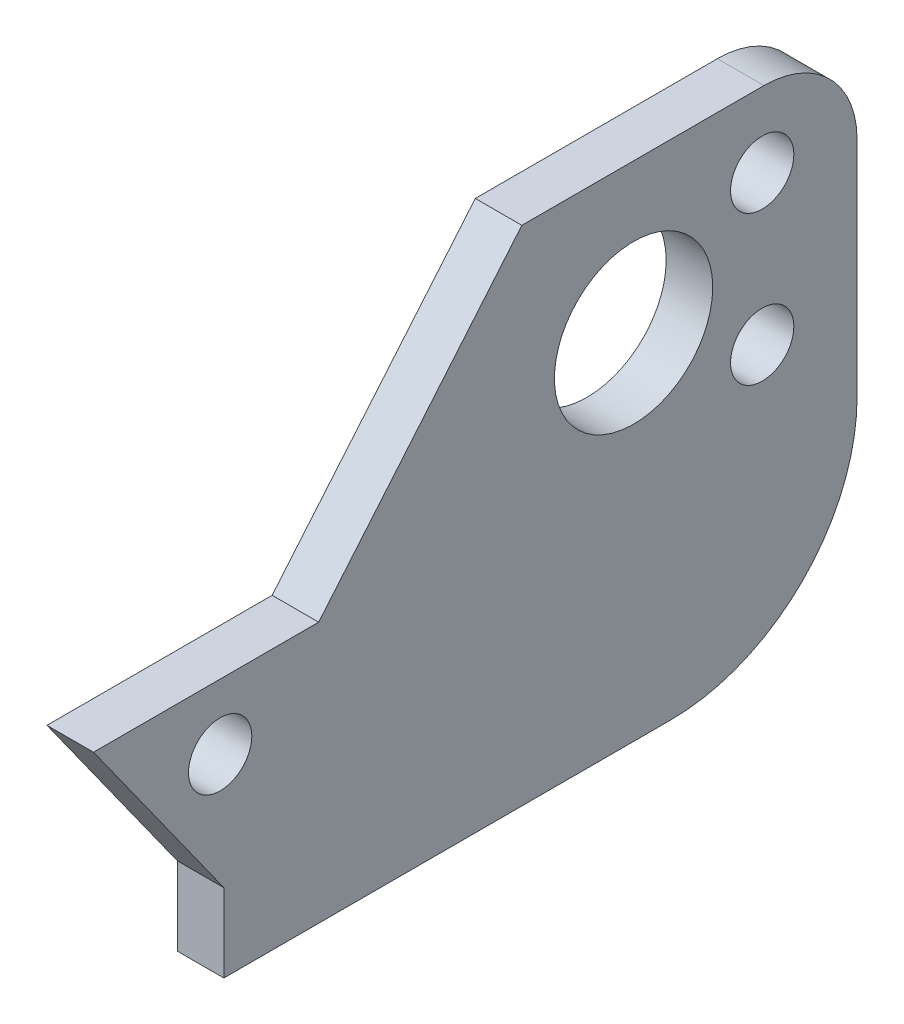
SolidWorks part; units mm, degrees
material "Plain Carbon Steel"
ref_plane "Front Plane" through (0, 0, 0) normal (0, 0, 1) x (1, 0, 0)
ref_plane "Top Plane" through (0, 0, 0) normal (0, 1, 0) x (1, 0, 0)
ref_plane "Right Plane" through (0, 0, 0) normal (1, 0, 0) x (0, 0, -1)
sketch "Sketch1" plane through (0, 0, 0) normal (1, 0, 0) x (0, 0, -1)
  line L0 (-45.1764, 3.0469) -> (-38.7478, -5.9531)
  line L1 (-36.7135, -7) -> (0, -7)
  line L3 (-43.142, 7) -> (0, 7)
  line L4 (0, -7) -> (0, 7)
  line L6 (-18, 20) -> (0, 20)
  line L7 (0, 20) -> (0, 7)
  line L8 (-18, 20) -> (-28.9083, 7)
  arc A2 (-38.7478, -5.9531) -> (-36.7135, -7) centre (-36.7135, -4.5) ccw
  arc A3 (-45.1764, 3.0469) -> (-43.142, 7) centre (-43.142, 4.5) cw
  circle A5 centre (-37.7061, -2.25) radius 1.5
  point P0 (0, 0)
  point P2 (0, 0)
  point P11 (0, 7)
  point P14 (-38, -7)
  point P17 (-48, 7)
  dimension "D4" = 2.5
  dimension "D5" = 3
  dimension "D9" = 4.75
  dimension "D1" = 14
  dimension "D2" = 48
  dimension "D3" = 10
  dimension "D6" = 27
  dimension "D7" = 18
  dimension "D8" = 50
  dimension "D10" = 3
extrude "Boss-Extrude1" add sketch "Sketch1" along normal mid plane 18 contours L7 L6 L3 | A3 L0 A2 L1 L4 L3 region at (0, 0.2529, 21.1769) region at (0, 12.9962, 11.9385)
sketch "Sketch2" plane through (0, 7, 0) normal (0, 1, 0) x (1, 0, 0)
  line L0 (9, -43.142) -> (-9, -43.142) construction
  line L1 (3, -47.142) -> (-3, -47.142)
  line L2 (3, -47.142) -> (3, -43.142)
  line L3 (3, -43.142) -> (-3, -43.142)
  line L4 (-3, -47.142) -> (-3, -43.142)
  line L5 (3, -47.142) -> (-3, -43.142) construction
  line L6 (3, -43.142) -> (-3, -47.142) construction
  point P0 (0, -45.142)
  dimension "D1" = 4
  dimension "D2" = 6
extrude "Boss-Extrude2" add sketch "Sketch2" against normal blind 6
sketch "Sketch3" plane through (3, 0, 0) normal (1, 0, 0) x (0, 0, -1)
  line L0 (-47.142, 1) -> (-47.142, 7) construction
  line L1 (-47.142, 1) -> (-43.7143, 1) construction
  circle A0 centre (-44.142, 4) radius 1.5
  dimension "D1" = 3
  dimension "D2" = 3
  dimension "D3" = 3
extrude "Cut-Extrude1" cut sketch "Sketch3" against normal up to next
fillet "Fillet1" radius 3 2 edges at (0, 1, 47.142) (0, 7, 47.142)
ref_plane "Plane1" through (0, 0, 0) normal (1, 0, 0) x (0, 0, -1)
sketch "Sketch5" plane through (0, 0, 0) normal (1, 0, 0) x (0, 0, -1)
  line L0 (0, 20) -> (0, -7) construction
  line L1 (-18, 20) -> (0, 20) construction
  line L5 (-30.5, -8) -> (6.5, -8)
  line L6 (-30.5, -8) -> (-30.5, 32)
  line L7 (-30.5, 32) -> (6.5, 32)
  line L8 (6.5, -8) -> (6.5, 32)
  line L9 (-30.5, -8) -> (6.5, 32) construction
  line L10 (-30.5, 32) -> (6.5, -8) construction
  circle A0 centre (-12, 12) radius 4.25
  dimension "D1" = 8.5
  dimension "D2" = 12
  dimension "D3" = 37
  dimension "D4" = 8
  dimension "D5" = 40
extrude "Cut-Extrude4" cut sketch "Sketch5" along normal mid plane 13 contours L5 L8 L7 L6 | A0 region at (0, 12, 29.9551)
extrude "Cut-Extrude5" cut sketch "Sketch5<3>" against normal mid plane 25 contours A0
sketch "Sketch5<3>" plane through (0, 0, 0) normal (1, 0, 0) x (0, 0, -1) same geometry as "Sketch5"
fillet "Fillet2" radius 5 1 edges at (-7.75, 20, 0)
sketch "Sketch6" plane through (9, 0, 0) normal (1, 0, 0) x (0, 0, -1)
  line L0 (-48, 7) -> (-38, -7)
  line L8 (-45.1764, 3.0469) -> (-38.7478, -5.9531) construction
  line L9 (-41, 7) -> (-34, -2.8)
  line L11 (-48, 7) -> (-41, 7)
  line L17 (-43.142, 7) -> (-28.9083, 7) construction
  line L18 (-36.7135, -7) -> (0, -7) construction
  line L19 (-34, -2.8) -> (-34, -7)
  line L21 (-38, -7) -> (-34, -7)
  point P0 (-28.9083, 7)
  dimension "D1" = 7
  dimension "D2" = 4
extrude "Cut-Extrude8" cut sketch "Sketch6" against normal up to surface (6 mm away) up to face at (3, 3.9168, 44.9927)
sketch "Sketch8" plane through (-9, 0, 0) normal (-1, 0, 0) x (0, 0, 1)
  line L2 (38, -7) -> (48, 7)
  line L4 (48, 7) -> (41, 7)
  line L5 (43.142, 7) -> (28.9083, 7) construction
  line L6 (41, 7) -> (34, -2.8)
  line L7 (34, -2.8) -> (34, -7)
  line L8 (36.7135, -7) -> (0, -7) construction
  line L9 (34, -7) -> (38, -7)
  dimension "D1" = 7
  dimension "D2" = 4
extrude "Cut-Extrude9" cut sketch "Sketch8" against normal up to surface (6 mm away) up to face at (-3, 3.9168, 44.9927)
sketch "Sketch9" plane through (9, 0, 0) normal (1, 0, 0) x (0, 0, -1)
  line L0 (-5.0949, 16) -> (-5.0949, 8) construction
  arc A1 (-5.0949, 8) -> (-5.0949, 16) centre (-12, 12) ccw
  circle A4 centre (-5.0949, 8) radius 1.7
  circle A5 centre (-5.0949, 16) radius 1.7
  circle A9 centre (-12, 12) radius 4.25 construction
  dimension "D1" = 7.98
  dimension "D4" = 3.4
  dimension "D2" = 8
extrude "Cut-Extrude10" cut sketch "Sketch9" against normal through all contours A4 | A5 | A5 region at (9, 16.9001, 6.4801) region at (9, 8.9001, 3.7097)
fillet "Fillet3" radius 10 1 edges at (-7.75, -7, 0)
sketch "Sketch4" plane through (0, -7, 0) normal (0, -1, 0) x (1, 0, 0)
  line L0 (-9, 34) -> (-9, 10) construction
  line L1 (1.5, 34) -> (-1.5, 34)
  line L2 (1.5, 34) -> (1.5, 43.7342)
  line L3 (1.5, 43.7342) -> (-1.5, 43.7342)
  line L4 (-1.5, 34) -> (-1.5, 43.7342)
  line L5 (1.5, 34) -> (-1.5, 43.7342) construction
  line L6 (1.5, 43.7342) -> (-1.5, 34) construction
  line L9 (3, 34) -> (9, 34) construction
  line L12 (-3, 43.7342) -> (3, 43.7342) construction
  point P0 (0, 38.8671)
  dimension "D2" = 3
  dimension "D4" = 9
extrude "Cut-Extrude3" cut sketch "Sketch4" against normal blind 8
sketch "Sketch11" plane through (-9, 0, 0) normal (-1, 0, 0) x (0, 0, 1)
  line L2 (34.1988, 7) -> (34.1988, 3.5) construction
  line L3 (41, 7) -> (28.9083, 7) construction
  line L4 (34.1988, 3.5) -> (37.0469, 1.4657) construction
  line L5 (41, 7) -> (34, -2.8) construction
  circle A0 centre (34.1988, 3.5) radius 1.7
  dimension "D3" = 3.4
  dimension "D1" = 3.5
extrude "Cut-Extrude11" cut sketch "Sketch11" against normal through all
sketch "Sketch12" plane through (0, 0, 0) normal (1, 0, 0) x (0, 0, -1)
  line L0 (-41, 7) -> (-28.9083, 7) construction
  line L1 (-48.4083, -8) -> (1.5917, -8)
  line L2 (-48.4083, -8) -> (-48.4083, 22)
  line L3 (-48.4083, 22) -> (1.5917, 22)
  line L4 (1.5917, -8) -> (1.5917, 22)
  line L5 (-48.4083, -8) -> (1.5917, 22) construction
  line L6 (-48.4083, 22) -> (1.5917, -8) construction
  point P0 (-23.4083, 7)
  dimension "D1" = 50
  dimension "D2" = 30
  dimension "D3" = 5.5
extrude "Cut-Extrude12" cut sketch "Sketch12" against normal up to surface (6.5 mm away) and the other way through all up to face at (-6.5, 8, 3.3949)
